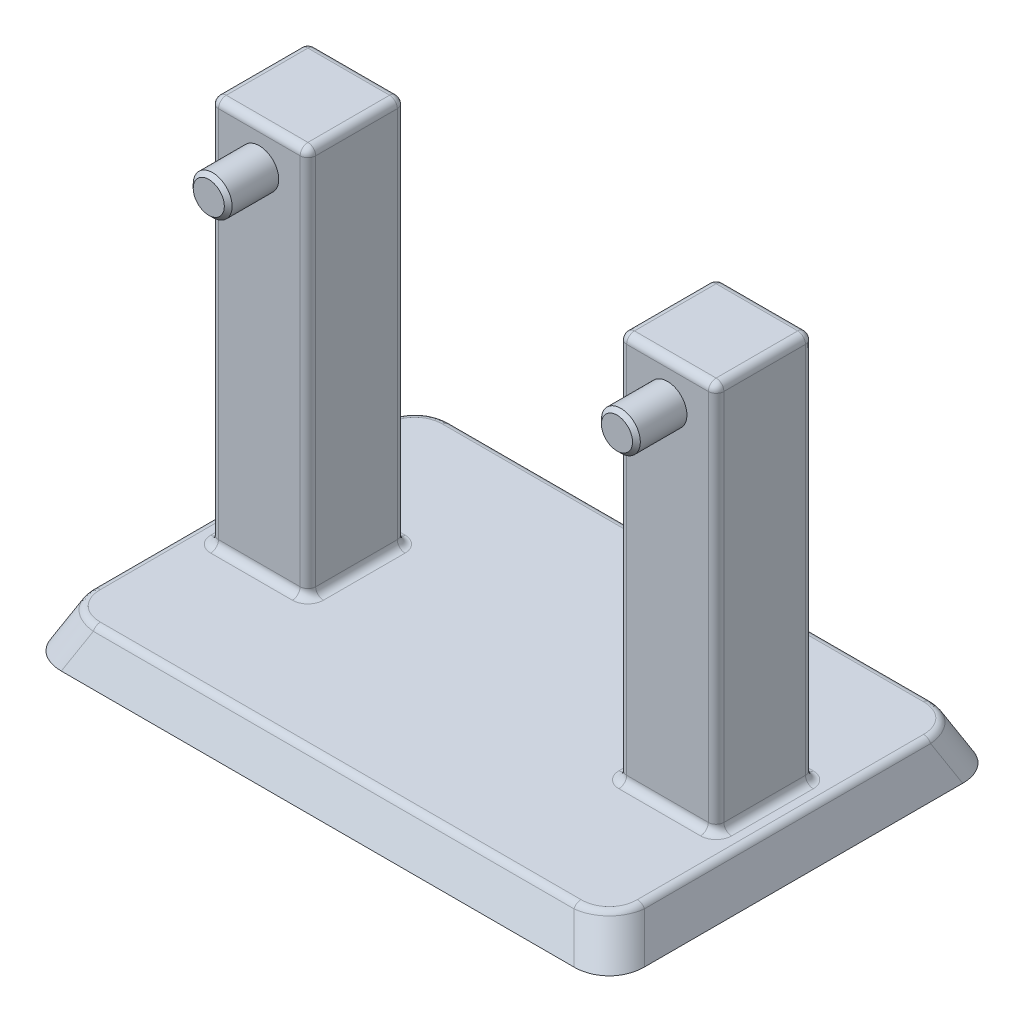
SolidWorks part; units mm, degrees
ref_plane "Přední rovina" through (0, 0, 0) normal (0, 0, 1) x (1, 0, 0)
ref_plane "Horní rovina" through (0, 0, 0) normal (0, 1, 0) x (1, 0, 0)
ref_plane "Pravá rovina" through (0, 0, 0) normal (1, 0, 0) x (0, 0, -1)
sketch "Skica1" plane through (0, 0, 0) normal (0, 1, 0) x (1, 0, 0)
  line L1 (-75, -50) -> (75, -50)
  line L2 (-75, -50) -> (-75, 50)
  line L3 (-75, 50) -> (75, 50)
  line L4 (75, -50) -> (75, 50)
  line L5 (-75, -50) -> (75, 50) construction
  line L6 (-75, 50) -> (75, -50) construction
  point P0 (0, 0)
  dimension "D1" = 150
  dimension "D2" = 100
extrude "Přidat vysunutím1" add sketch "Skica1" along normal blind 10 draft 25
shell "Skořepina1" thickness 3 removed face at (0, 0, 0)
sketch "Skica2" plane through (0, 10, 0) normal (0, 1, 0) x (1, 0, 0)
  line L1 (40, 12.5) -> (65, 12.5)
  line L2 (40, 12.5) -> (40, -12.5)
  line L3 (40, -12.5) -> (65, -12.5)
  line L4 (65, 12.5) -> (65, -12.5)
  line L5 (40, 12.5) -> (65, -12.5) construction
  line L6 (40, -12.5) -> (65, 12.5) construction
  point P0 (52.5, 0)
  dimension "D1" = 25
  dimension "D2" = 52.5
extrude "Přidat vysunutím2" add sketch "Skica2" along normal blind 100
sketch "Skica3" plane through (0, 0, 12.5) normal (0, 0, 1) x (1, 0, 0)
  line L0 (40, 110) -> (65, 110) construction
  circle A0 centre (52.5, 100) radius 5
  point P5 (52.5, 110)
  dimension "D1" = 10
  dimension "D2" = 10
extrude "Přidat vysunutím3" add sketch "Skica3" along normal blind 13
mirror "Zrcadlit1" about plane through (0, 0, 0) normal (1, 0, 0) of "Přidat vysunutím3", "Přidat vysunutím2"
fillet "Zaoblit1" radius 10 4 edges at (-72.6685, 5, 47.6685) (-72.6685, 5, -47.6685) (72.6685, 5, -47.6685) (72.6685, 5, 47.6685)
fillet "Zaoblit2" radius 2 8 edges at (0, 10, 45.3369) (-67.7733, 10, 42.7733) (-70.3369, 10, 0) (-67.7733, 10, -42.7733) (0, 10, -45.3369) (67.7733, 10, -42.7733) (70.3369, 10, 0) (67.7733, 10, 42.7733)
fillet "Zaoblit3" radius 2 8 edges at (65, 60, -12.5) (40, 60, -12.5) (40, 60, 12.5) (65, 60, 12.5) (-40, 60, -12.5) (-65, 60, -12.5) (-65, 60, 12.5) (-40, 60, 12.5)
fillet "Zaoblit4" radius 2 32 edges at (-40.5858, 110, -11.9142) (-52.5, 110, -12.5) (-64.4142, 110, -11.9142) (-65, 110, 0) (-64.4142, 110, 11.9142) (-52.5, 110, 12.5) (-40.5858, 110, 11.9142) (64.4142, 110, 11.9142) (52.5, 110, 12.5) (40.5858, 110, 11.9142) (40, 110, 0) (40.5858, 110, -11.9142) (52.5, 110, -12.5) (64.4142, 110, -11.9142) (64.4142, 10, 11.9142) (52.5, 10, 12.5) (40.5858, 10, 11.9142) (40, 10, 0) (40.5858, 10, -11.9142) (52.5, 10, -12.5) (64.4142, 10, -11.9142) (-40.5858, 10, -11.9142) (-52.5, 10, -12.5) (-64.4142, 10, -11.9142) (-65, 10, 0) (-64.4142, 10, 11.9142) (-52.5, 10, 12.5) (-40.5858, 10, 11.9142) (-40, 110, 0) (65, 110, 0) (65, 10, 0) (-40, 10, 0)
chamfer "Zkosení1" distance 1 angle 45 2 edges at (57.5, 100, 25.5) (-57.5, 100, 25.5)
